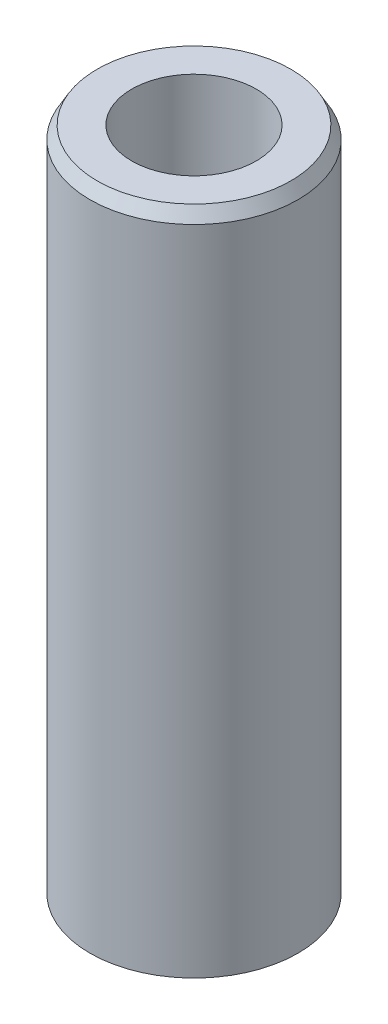
SolidWorks part; units mm, degrees
ref_plane "Front Plane" through (0, 0, 0) normal (0, 0, 1) x (1, 0, 0)
ref_plane "Top Plane" through (0, 0, 0) normal (0, 1, 0) x (1, 0, 0)
ref_plane "Right Plane" through (0, 0, 0) normal (1, 0, 0) x (0, 0, -1)
sketch "Sketch1" plane through (0, 0, 0) normal (0, 1, 0) x (1, 0, 0)
  circle A0 centre (0, 0) radius 10
  dimension "SHAFT_OD" = 20
extrude "Boss-Extrude1" add sketch "Sketch1" along normal blind 64.6007
sketch "Sketch2" plane through (0, 0, 0) normal (0, 1, 0) x (1, 0, 0)
  circle A0 centre (0, 0) radius 5.9851
  dimension "BORE_D" = 11.9702
extrude "Cut-Extrude1" cut sketch "Sketch2" along normal through all
chamfer "Chamfer1" distance 1.2103 angle 30 2 edges at (0, 64.6007, 10) (0, 0, 10) first distance on face at (0, 64.6007, 10) first distance on face at (0, 0, 5.9851)
